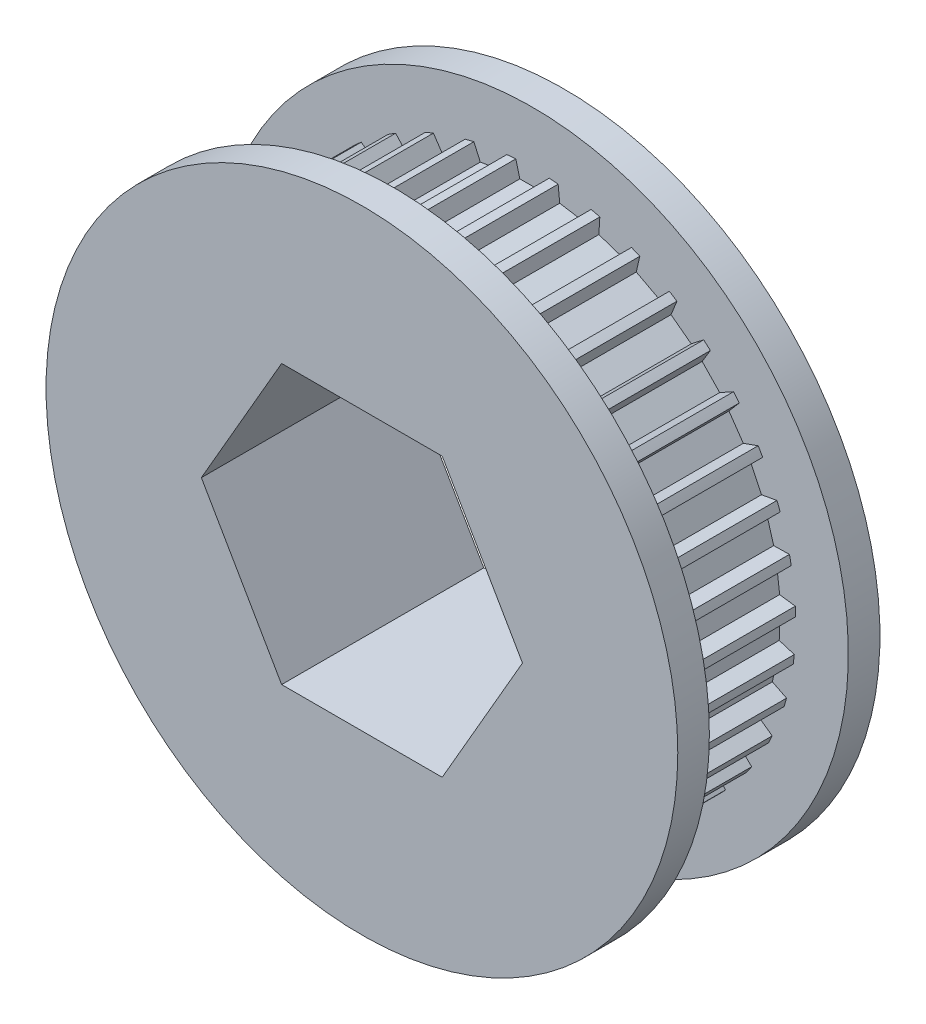
SolidWorks part; units mm, degrees
ref_plane "Front Plane" through (0, 0, 0) normal (0, 0, 1) x (1, 0, 0)
ref_plane "Top Plane" through (0, 0, 0) normal (0, 1, 0) x (1, 0, 0)
ref_plane "Right Plane" through (0, 0, 0) normal (1, 0, 0) x (0, 0, -1)
sketch "Sketch1" plane through (0, 0, 0) normal (0, 0, 1) x (1, 0, 0)
  circle A0 centre (0, 0) radius 12.5
  dimension "D1" = 25
extrude "Boss-Extrude1" add sketch "Sketch1" along normal mid plane 6.6
sketch "Sketch3" plane through (0, 0, 3.3) normal (0, 0, 1) x (1, 0, 0)
  circle A0 centre (0, 0) radius 15
  dimension "D1" = 30
sketch "Sketch2" plane through (0, 0, -3.3) normal (0, 0, -1) x (-1, 0, 0)
  circle A0 centre (0, 0) radius 15
  dimension "D1" = 30
sketch "Sketch4" plane through (0, 0, 3.3) normal (0, 0, 1) x (1, 0, 0)
  line L0 (-0.6, 11.75) -> (0.6, 11.75)
  line L1 (0.6, 11.75) -> (0.8, 12.5)
  line L2 (0.8, 12.5) -> (-0.8, 12.5)
  line L3 (-0.8, 12.5) -> (-0.6, 11.75)
  circle A0 centre (0, 0) radius 12.5 construction
  point P10 (0, 11.75)
  dimension "D1" = 1.2
  dimension "D2" = 1.6
  dimension "D3" = 0.75
extrude "Cut-Extrude1" cut sketch "Sketch4" against normal up to surface (6.6 mm away) and the other way through all up to face at (12.5, 0, -3.3)
pattern_circular "CirPattern2" count 39 over 360 about axis through (0, 0, 3.3) along (0, 0, 1) of "Cut-Extrude1"
extrude "Boss-Extrude3" add sketch "Sketch2" along normal blind 1.5
extrude "Boss-Extrude4" add sketch "Sketch3" along normal blind 1.5 contours A0
sketch "Sketch5" plane through (0, 0, 4.8) normal (0, 0, 1) x (1, 0, 0)
  line L1 (7.625, 0) -> (3.8125, 6.6034)
  line L2 (3.8125, 6.6034) -> (-3.8125, 6.6034)
  line L3 (-3.8125, 6.6034) -> (-7.625, 0)
  line L4 (-7.625, 0) -> (-3.8125, -6.6034)
  line L5 (-3.8125, -6.6034) -> (3.8125, -6.6034)
  line L6 (3.8125, -6.6034) -> (7.625, 0)
  circle A0 centre (0, 0) radius 6.6034 construction
  dimension "D1" = 15.25
extrude "Cut-Extrude2" cut sketch "Sketch5" against normal through all both and the other way through all
